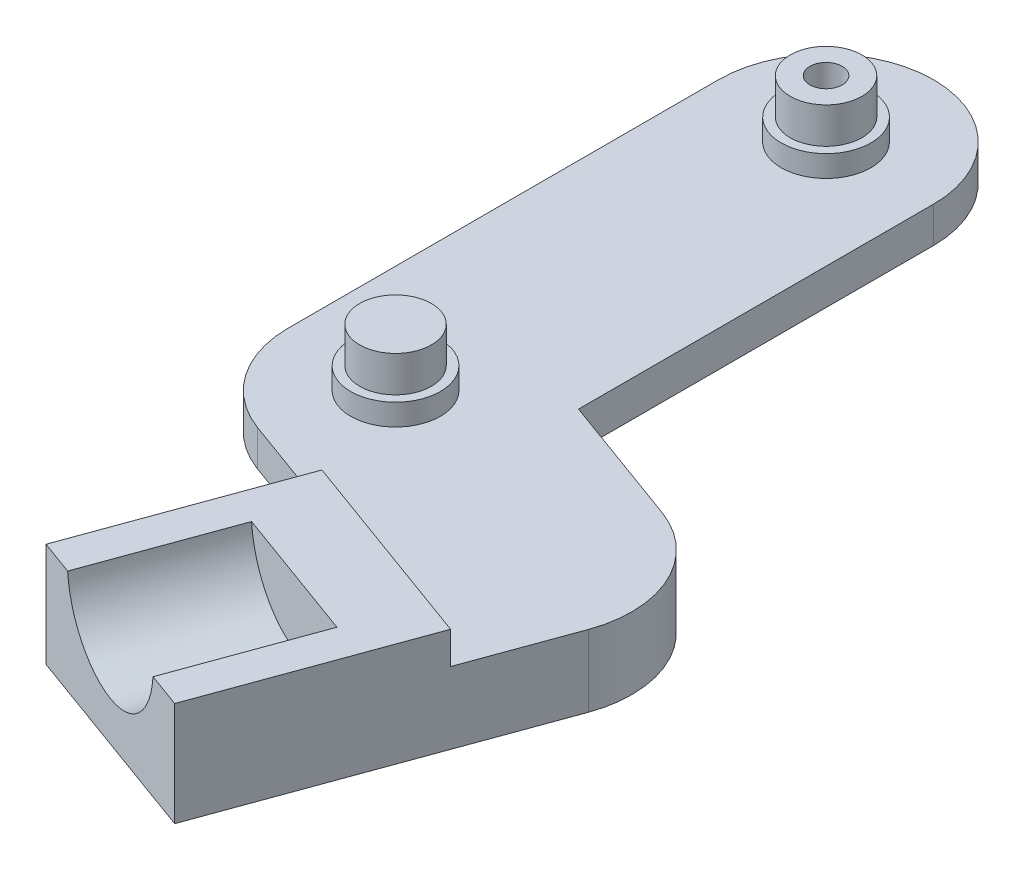
SolidWorks part; units mm, degrees
material "7075-T6 (SN)"
ref_plane "정면" through (0, 0, 0) normal (0, 0, 1) x (1, 0, 0)
ref_plane "윗면" through (0, 0, 0) normal (0, 1, 0) x (1, 0, 0)
ref_plane "우측면" through (0, 0, 0) normal (1, 0, 0) x (0, 0, -1)
sketch "스케치1" plane through (0, 0, 0) normal (0, 1, 0) x (1, 0, 0)
  line L0 (0, 0) -> (0, 60) construction
  line L1 (-15, 0) -> (-15, 60)
  line L2 (15, 0) -> (15, 60)
  arc A0 (-15, 0) -> (15, 0) centre (0, 0) ccw
  arc A1 (15, 60) -> (-15, 60) centre (0, 60) ccw
  point P3 (0, 30)
  dimension "D2" = 15
  dimension "D1" = 60
extrude "보스-돌출1" add sketch "스케치1" along normal blind 5 contours A1 L1 A0 L2
sketch "스케치2" plane through (0, 5, 0) normal (0, 1, 0) x (1, 0, 0)
  line L0 (0, 60) -> (0, 0) construction
  circle A0 centre (0, 60) radius 6.25
  circle A1 centre (0, 0) radius 6.25
  dimension "D2" = 12.5
  dimension "D3" = 12.5
  dimension "D1" = 60
extrude "보스-돌출2" add sketch "스케치2" along normal blind 3
sketch "스케치3" plane through (0, 8, 0) normal (0, 1, 0) x (1, 0, 0)
  circle A0 centre (0, 60) radius 5
  circle A1 centre (0, 0) radius 5
  dimension "D1" = 10
  dimension "D2" = 10
extrude "보스-돌출3" add sketch "스케치3" along normal blind 5
sketch "스케치4" plane through (0, 0, 0) normal (0, -1, 0) x (1, 0, 0)
  line L0 (0, -60) -> (0, 5) construction
  dimension "D1" = 65
hole_wizard "M4 남비 머리 나사용 카운터보어1" positions "스케치5" profile "스케치7" counterbore size "M4" standard "ISO" end condition through all
sketch "스케치5" plane through (0, 0, 0) normal (0, -1, 0) x (-1, 0, 0)
  point P3 (0, 60)
  point P10 (0, -25)
  dimension "D1" = 85
sketch "스케치7" plane through (0, 0, -60) normal (1, 0, 0) x (0, 0, -1)
  line L0 (0, 0) -> (0, 13)
  line L1 (0, 13) -> (2.25, 13)
  line L3 (2.25, 13) -> (2.25, 4)
  line L4 (2.25, 4) -> (4.5, 4)
  line L5 (4.5, 4) -> (4.5, 0)
  line L7 (4.5, 0) -> (0, 0)
  line L11 (0, -6.35) -> (0, 107.95) construction
  dimension "관통 구멍 지름" = 4.5
  dimension "관통 구멍 깊이" = 13
  dimension "카운터보어 지름" = 9
  dimension "카운터보어 깊이" = 4
sketch "스케치8" plane through (0, 0, 0) normal (0, -1, 0) x (1, 0, 0)
  line L0 (0, 0) -> (28.1908, 10.2606) construction
  line L1 (15, 0) -> (15, -60) construction
  line L2 (0, 0) -> (28.1908, 10.2606) construction
  line L3 (-5.1303, 14.0954) -> (23.0605, 24.356)
  line L4 (15, -10.5031) -> (33.3211, -3.8348)
  line L5 (15, 0) -> (15, -10.5031)
  arc A1 (33.3211, -3.8348) -> (23.0605, 24.356) centre (28.1908, 10.2606) ccw
  arc A2 (15, 0) -> (-15, 0) centre (0, 0) ccw construction
  arc A3 (15, 0) -> (-5.1303, 14.0954) centre (0, 0) ccw
  point P3 (15, 5.4596)
  dimension "D3" = 15
  dimension "D1" = 110
  dimension "D2" = 30
extrude "보스-돌출4" add sketch "스케치8" against normal blind 5
sketch "스케치9" plane through (0, 0, 0) normal (0, -1, 0) x (1, 0, 0)
  line L0 (28.1908, 10.2606) -> (17.9302, 38.4514) construction
  line L1 (23.0605, 24.356) -> (-5.1303, 14.0954) construction
  line L2 (28.1908, 10.2606) -> (17.9302, 38.4514) construction
  line L3 (14.0954, 5.1303) -> (3.8348, 33.3211)
  line L4 (42.2862, 15.3909) -> (32.0256, 43.5817)
  line L5 (3.8348, 33.3211) -> (-1.2955, 47.4165)
  line L6 (32.0256, 43.5817) -> (26.8953, 57.6771)
  line L7 (-1.2955, 47.4165) -> (26.8953, 57.6771)
  arc A0 (14.0954, 5.1303) -> (42.2862, 15.3909) centre (28.1908, 10.2606) ccw
  point P5 (23.0605, 24.356)
  dimension "D3" = 15
  dimension "D5" = 30
  dimension "D1" = 30
  dimension "D2" = 90
  dimension "D4" = 45
  dimension "D6" = 30
extrude "보스-돌출5" add sketch "스케치9" against normal blind 5 and the other way blind 5
sketch "스케치13" plane through (0, 5, 0) normal (0, 1, 0) x (1, 0, 0)
  line L0 (42.2862, -15.3909) -> (26.8953, -57.6771) construction
  line L1 (-1.2955, -47.4165) -> (8.9651, -19.2257) construction
  line L2 (26.8953, -57.6771) -> (-1.2955, -47.4165) construction
  line L3 (37.1559, -29.4863) -> (26.8953, -57.6771)
  line L4 (-1.2955, -47.4165) -> (8.9651, -19.2257)
  line L5 (26.8953, -57.6771) -> (-1.2955, -47.4165)
  line L6 (8.9651, -19.2257) -> (37.1559, -29.4863)
extrude "보스-돌출6" add sketch "스케치13" along normal blind 4.5
sketch "스케치15" plane through (-15.3909, 0, 42.2862) normal (-0.342, 0, 0.9397) x (0.9397, 0, 0.342)
  line L0 (15, 9.5) -> (45, 9.5) construction
  line L1 (14.3731, 10.5) -> (45.6844, 10.5) construction
  line L2 (45, -5) -> (45, 9.5) construction
  circle A0 centre (30, 10.5) radius 10
  dimension "D1" = 20
  dimension "D2" = 1
  dimension "D3" = 15
extrude "컷-돌출2" cut sketch "스케치15" against normal blind 20
